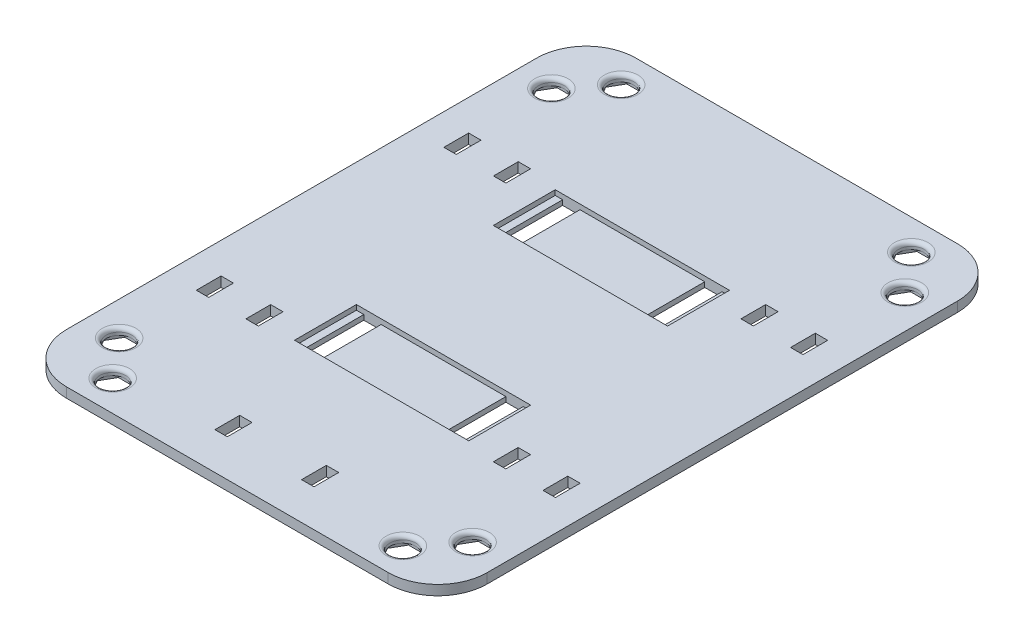
SolidWorks part; units mm, degrees
material "3-D Printed ABS"
ref_plane "Front Plane" through (0, 0, 0) normal (0, 0, 1) x (1, 0, 0)
ref_plane "Top Plane" through (0, 0, 0) normal (0, 1, 0) x (1, 0, 0)
ref_plane "Right Plane" through (0, 0, 0) normal (1, 0, 0) x (0, 0, -1)
sketch "Sketch1" plane through (0, 0, 0) normal (0, 1, 0) x (1, 0, 0)
  line L1 (-53.975, -73.025) -> (53.975, -73.025)
  line L2 (-53.975, -73.025) -> (-53.975, 73.025)
  line L3 (-53.975, 73.025) -> (53.975, 73.025)
  line L4 (53.975, -73.025) -> (53.975, 73.025)
  line L5 (-53.975, -73.025) -> (53.975, 73.025) construction
  line L6 (-53.975, 73.025) -> (53.975, -73.025) construction
  point P0 (0, 0)
  dimension "D1" = 107.95
  dimension "PlateY" = 146.05
extrude "Boss-Extrude1" add sketch "Sketch1" against normal blind 2.54
sketch "Sketch2" plane through (0, 0, 0) normal (0, 1, 0) x (1, 0, 0)
  line L0 (0, 0) -> (152.4, 0) construction
  line L1 (0, 0) -> (0, 152.4) construction
  line L4 (0, 0) -> (-53.975, 73.025) construction
  line L5 (0, 0) -> (-152.4, 0) construction
  line L6 (0, 0) -> (-152.4, 152.4) construction
  line L7 (-53.975, 73.025) -> (-53.975, -73.025) construction
  line L8 (53.975, 73.025) -> (-53.975, 73.025) construction
  line L9 (-152.4, 152.4) -> (-41.275, 60.325) construction
  line L10 (-41.275, 60.325) -> (0, 26.1257) construction
  line L11 (-30.7521, 73.025) -> (-53.975, 44.9974) construction
  circle A0 centre (-37.2189, 65.2108) radius 3.302
  circle A1 centre (45.3264, 55.4354) radius 3.302
  circle A2 centre (37.2189, 65.2108) radius 3.302
  circle A3 centre (-45.3264, -55.4354) radius 3.302
  circle A4 centre (-45.3264, 55.4354) radius 3.302
  circle A5 centre (-37.2189, -65.2108) radius 3.302
  circle A6 centre (37.2189, -65.2108) radius 3.302
  circle A7 centre (45.3264, -55.4354) radius 3.302
  point P12 (-41.275, 60.325)
  point P15 (-37.2189, 65.2108)
  dimension "D1" = 6.604
  dimension "D3" = 12.7
  dimension "D8" = 6.604
  dimension "D2" = 12.7
  dimension "D4" = 152.4
  dimension "D5" = 152.4
  dimension "D6" = 152.4
  dimension "D7" = 6.35
  dimension "D9" = 6.35
extrude "Cut-Extrude1" cut sketch "Sketch2" against normal through all
sketch "Sketch3" plane through (0, 0, 0) normal (0, 1, 0) x (1, 0, 0)
  line L0 (-53.975, 0) -> (53.975, 0) construction
  line L1 (-20.445, 33.4374) -> (-16, 33.4374)
  line L2 (-20.445, 33.4374) -> (-20.445, 17.5624)
  line L3 (-20.445, 17.5624) -> (-16, 17.5624)
  line L4 (-16, 33.4374) -> (-16, 17.5624)
  line L5 (16, 33.4374) -> (16, 17.5624)
  line L6 (20.445, 17.5624) -> (16, 17.5624)
  line L7 (20.445, 33.4374) -> (20.445, 17.5624)
  line L8 (20.445, 33.4374) -> (16, 33.4374)
  line L9 (-53.975, 73.025) -> (-53.975, -73.025) construction
  line L10 (53.975, -73.025) -> (53.975, 73.025) construction
  line L11 (0, -25.4999) -> (0, 79.6704) construction
  line L12 (0, 25.4999) -> (0, -79.6704) construction
  line L13 (20.445, -33.4374) -> (16, -33.4374)
  line L14 (20.445, -33.4374) -> (20.445, -17.5624)
  line L15 (20.445, -17.5624) -> (16, -17.5624)
  line L16 (16, -33.4374) -> (16, -17.5624)
  line L17 (-16, -33.4374) -> (-16, -17.5624)
  line L18 (-20.445, -17.5624) -> (-16, -17.5624)
  line L19 (-20.445, -33.4374) -> (-20.445, -17.5624)
  line L20 (-20.445, -33.4374) -> (-16, -33.4374)
  line L21 (-20.445, 25.4999) -> (-32.442, 25.4999) construction
  line L22 (-53.975, -73.025) -> (53.975, -73.025) construction
  point P31 (0, -73.025)
  point P32 (-53.975, 0)
  dimension "D1" = 15.875
  dimension "D2" = 4.445
  dimension "D3" = 16
  dimension "D4" = 25.4999
  dimension "D5" = 25.4999
extrude "Cut-Extrude2" cut sketch "Sketch3" against normal through all
fillet "Fillet1" radius 12.7 4 edges at (53.975, -1.27, -73.025) (53.975, -1.27, 73.025) (-53.975, -1.27, 73.025) (-53.975, -1.27, -73.025)
sketch "Sketch4" plane through (0, 0, 0) normal (0, 1, 0) x (1, 0, 0)
  line L0 (0, 0) -> (80.9727, -80.9727) construction
  line L1 (0, 0) -> (-80.9727, -80.9727) construction
  line L2 (69.1118, -51.1513) -> (28.7006, -10.7401)
  line L3 (28.7006, -10.7401) -> (10.7401, -28.7006)
  line L4 (10.7401, -28.7006) -> (51.1513, -69.1118)
  line L5 (51.1513, -69.1118) -> (69.1118, -51.1513)
  line L6 (0, 0) -> (0, -118.7381) construction
  line L7 (0, 0) -> (-98.4177, 0) construction
  line L8 (-51.1513, -69.1118) -> (-69.1118, -51.1513)
  line L9 (-69.1118, -51.1513) -> (-28.7006, -10.7401)
  line L10 (-28.7006, -10.7401) -> (-10.7401, -28.7006)
  line L11 (-10.7401, -28.7006) -> (-51.1513, -69.1118)
  line L12 (-69.1118, 51.1513) -> (-28.7006, 10.7401)
  line L13 (-51.1513, 69.1118) -> (-69.1118, 51.1513)
  line L14 (-10.7401, 28.7006) -> (-51.1513, 69.1118)
  line L15 (-28.7006, 10.7401) -> (-10.7401, 28.7006)
  line L16 (51.1513, 69.1118) -> (69.1118, 51.1513)
  line L17 (69.1118, 51.1513) -> (28.7006, 10.7401)
  line L18 (28.7006, 10.7401) -> (10.7401, 28.7006)
  line L19 (10.7401, 28.7006) -> (51.1513, 69.1118)
  point P6 (19.7204, -19.7204)
  dimension "D1" = 25.4
  dimension "D2" = 57.15
  dimension "D3" = 45
extrude "Cut-Extrude3" [suppressed] cut sketch "Sketch4" against normal blind 1.5875
sketch "Sketch6" [suppressed] plane through (0, 0, 0) normal (0, 1, 0) x (1, 0, 0)
  line L0 (46.3377, -44.1074) -> (34.6634, -32.4331) construction
  line L1 (0, 0) -> (0, -117.7376) construction
  line L2 (0, 0) -> (-151.7285, 0) construction
  line L4 (28.1601, -10.1996) -> (10.1996, -28.1601) construction
  line L5 (50.6107, -68.5712) -> (68.5712, -50.6107) construction
  text T0 "ESC" font "Century Gothic" height in points 22
  dimension "D1" = 45
  dimension "D2" = 20.32
  dimension "D3" = 20.32
extrude "Cut-Extrude5" [suppressed] cut sketch "Sketch6" against normal blind 3.175
sketch "Sketch5" plane through (0, 0, 0) normal (0, 1, 0) x (1, 0, 0)
  line L0 (41.275, 73.025) -> (-41.275, 73.025) construction
  line L1 (14.2875, 15.875) -> (-14.2875, 15.875)
  line L2 (14.2875, 15.875) -> (14.2875, 66.675)
  line L3 (14.2875, 66.675) -> (-14.2875, 66.675)
  line L4 (-14.2875, 15.875) -> (-14.2875, 66.675)
  point P4 (0, 15.875)
  dimension "D1" = 50.8
  dimension "D2" = 28.575
  dimension "D3" = 6.35
extrude "Cut-Extrude4" [suppressed] cut sketch "Sketch5" against normal blind 1.5875
ref_axis "Axis1" through (0, 0.3175, 0) along (0, -1, 0)
pattern_circular "CirPattern1" [suppressed] count 4 over 360 about axis through (0, 0.3175, 0) along (0, -1, 0) of bodies 105
sketch "Sketch7" plane through (0, 0, 0) normal (0, 1, 0) x (1, 0, 0)
  line L0 (0, 0) -> (0, -54.962) construction
  line L1 (63.4018, -13.3522) -> (38.0018, -13.3522)
  line L2 (63.4018, -13.3522) -> (63.4018, 43.7978)
  line L3 (63.4018, 43.7978) -> (38.0018, 43.7978)
  line L4 (38.0018, -13.3522) -> (38.0018, 43.7978)
  line L5 (-38.0018, -13.3522) -> (-38.0018, 43.7978)
  line L6 (-63.4018, 43.7978) -> (-38.0018, 43.7978)
  line L7 (-63.4018, -13.3522) -> (-63.4018, 43.7978)
  line L8 (-63.4018, -13.3522) -> (-38.0018, -13.3522)
  line L9 (-41.275, -73.025) -> (41.275, -73.025) construction
  line L10 (38.5677, -40.64) -> (-18.5823, -40.64)
  line L11 (38.5677, -40.64) -> (38.5677, -66.04)
  line L12 (38.5677, -66.04) -> (-18.5823, -66.04)
  line L13 (-18.5823, -40.64) -> (-18.5823, -66.04)
  line L14 (38.5677, -40.64) -> (-18.5823, -66.04) construction
  line L15 (38.5677, -66.04) -> (-18.5823, -40.64) construction
  line L16 (19.844, -36.1003) -> (-37.306, -36.1003)
  line L17 (19.844, -36.1003) -> (19.844, -61.5003)
  line L18 (19.844, -61.5003) -> (-37.306, -61.5003)
  line L19 (-37.306, -36.1003) -> (-37.306, -61.5003)
  line L20 (19.844, -36.1003) -> (-37.306, -61.5003) construction
  line L21 (19.844, -61.5003) -> (-37.306, -36.1003) construction
  point P11 (9.9927, -53.34)
  point P18 (-8.731, -48.8003)
  dimension "D1" = 57.15
  dimension "D2" = 25.4
  dimension "D3" = 57.15
  dimension "D4" = 25.4
  dimension "D5" = 6.985
  dimension "D6" = 57.15
  dimension "D7" = 25.4
extrude "Cut-Extrude6" [suppressed] cut sketch "Sketch7" against normal blind 1.27
sketch "Sketch8" plane through (0, 0, 0) normal (0, 1, 0) x (1, 0, 0)
  line L7 (19.05, -31.75) -> (-19.05, -31.75)
  line L8 (19.05, -31.75) -> (19.05, 31.75)
  line L9 (19.05, 31.75) -> (-19.05, 31.75)
  line L10 (-19.05, -31.75) -> (-19.05, 31.75)
  point P0 (0, 0)
  dimension "D1" = 38.1
  dimension "D2" = 31.75
  dimension "D3" = 63.5
extrude "Boss-Extrude3" [suppressed] add sketch "Sketch8" along normal blind 2.54
sketch "Sketch11" plane through (0, 0, 0) normal (0, 1, 0) x (1, 0, 0)
  line L0 (-20.445, -33.4374) -> (-16, -33.4374) construction
  line L1 (22.35, -33.4374) -> (-22.35, -33.4374)
  line L2 (22.35, -33.4374) -> (22.35, -17.5624)
  line L3 (22.35, -17.5624) -> (-22.35, -17.5624)
  line L4 (-22.35, -33.4374) -> (-22.35, -17.5624)
  line L5 (20.445, -17.5624) -> (16, -17.5624) construction
  line L6 (20.445, -33.4374) -> (20.445, -17.5624) construction
  line L7 (-20.445, -17.5624) -> (-20.445, -33.4374) construction
  line L8 (0, 0) -> (90.9737, 0) construction
  line L9 (-22.35, 33.4374) -> (-22.35, 17.5624)
  line L10 (22.35, 17.5624) -> (-22.35, 17.5624)
  line L11 (22.35, 33.4374) -> (22.35, 17.5624)
  line L12 (22.35, 33.4374) -> (-22.35, 33.4374)
  dimension "D1" = 1.905
  dimension "D2" = 1.905
extrude "Cut-Extrude9" cut sketch "Sketch11" against normal mid plane 2.54
sketch "Sketch12" plane through (0, 0, 0) normal (0, 1, 0) x (1, 0, 0)
  line L1 (12.7, -41.6354) -> (-12.7, -41.6354)
  line L2 (12.7, -41.6354) -> (12.7, -25.4999)
  line L3 (12.7, -25.4999) -> (-12.7, -25.4999)
  line L4 (-12.7, -41.6354) -> (-12.7, -25.4999)
  line L6 (23.8125, 0) -> (-23.8125, 0) construction
  line L7 (-53.975, 60.325) -> (-53.975, -60.325) construction
  line L9 (-12.7, 41.6354) -> (-12.7, 25.4999)
  line L10 (12.7, 25.4999) -> (-12.7, 25.4999)
  line L11 (12.7, 41.6354) -> (12.7, 25.4999)
  line L12 (12.7, 41.6354) -> (-12.7, 41.6354)
  point P6 (-53.975, 0)
  dimension "D1" = 25.4
  dimension "D2" = 25.4999
extrude "Cut-Extrude12" [suppressed] cut sketch "Sketch12" along normal through all
sketch "Sketch9" plane through (0, 0, 0) normal (0, 1, 0) x (1, 0, 0)
  line L1 (25.1579, -52.4084) -> (-25.6421, -52.4084)
  line L2 (25.1579, -52.4084) -> (25.1579, -1.6084)
  line L3 (25.1579, -1.6084) -> (-25.6421, -1.6084)
  line L4 (-25.6421, -52.4084) -> (-25.6421, -1.6084)
  line L5 (25.1579, -52.4084) -> (-25.6421, -1.6084) construction
  line L6 (25.1579, -1.6084) -> (-25.6421, -52.4084) construction
  point P0 (-0.2421, -27.0084)
  dimension "D1" = 50.8
  dimension "D2" = 50.8
sketch "Sketch13" plane through (0, 0, 0) normal (0, 1, 0) x (1, 0, 0)
  line L0 (0, 0) -> (0, -106.7514) construction
  line L1 (34.925, 3.175) -> (28.575, 3.175)
  line L2 (34.925, 3.175) -> (34.925, -3.175)
  line L3 (34.925, -3.175) -> (28.575, -3.175)
  line L4 (28.575, 3.175) -> (28.575, -3.175)
  line L5 (34.925, 3.175) -> (28.575, -3.175) construction
  line L6 (34.925, -3.175) -> (28.575, 3.175) construction
  line L7 (-34.925, -3.175) -> (-28.575, 3.175) construction
  line L8 (-34.925, 3.175) -> (-28.575, -3.175) construction
  line L9 (-28.575, 3.175) -> (-28.575, -3.175)
  line L10 (-34.925, -3.175) -> (-28.575, -3.175)
  line L11 (-34.925, 3.175) -> (-34.925, -3.175)
  line L12 (-34.925, 3.175) -> (-28.575, 3.175)
  point P0 (31.75, 0)
  point P12 (-31.75, 0)
  dimension "D1" = 6.35
  dimension "D2" = 28.575
  dimension "D3" = 0
extrude "Cut-Extrude13" [suppressed] cut sketch "Sketch13" against normal through all
fillet "Fillet2" radius 1.016 8 edges at (-37.2189, 0, -61.9088) (37.2189, 0, 68.5128) (45.3264, 0, 58.7374) (-37.2189, 0, 61.9088) (-45.3264, 0, 52.1334) (45.3264, 0, -58.7374) (37.2189, 0, -68.5128) (-45.3264, 0, -52.1334)
sketch "Sketch14" plane through (0, 0, 0) normal (0, 1, 0) x (1, 0, 0)
  line L0 (0, 76.698) -> (0, -76.698) construction
  line L1 (33.3248, -34.925) -> (30.1498, -34.925)
  line L2 (33.3248, -34.925) -> (33.3248, -28.575)
  line L3 (33.3248, -28.575) -> (30.1498, -28.575)
  line L4 (30.1498, -34.925) -> (30.1498, -28.575)
  line L5 (0, 0) -> (-92.4571, 0) construction
  line L6 (-30.1498, -34.925) -> (-30.1498, -28.575)
  line L7 (-33.3248, -28.575) -> (-30.1498, -28.575)
  line L8 (-33.3248, -34.925) -> (-33.3248, -28.575)
  line L9 (-33.3248, -34.925) -> (-30.1498, -34.925)
  line L10 (-33.3248, 34.925) -> (-30.1498, 34.925)
  line L11 (-33.3248, 34.925) -> (-33.3248, 28.575)
  line L12 (-33.3248, 28.575) -> (-30.1498, 28.575)
  line L13 (-30.1498, 34.925) -> (-30.1498, 28.575)
  line L14 (30.1498, 34.925) -> (30.1498, 28.575)
  line L15 (33.3248, 28.575) -> (30.1498, 28.575)
  line L16 (33.3248, 34.925) -> (33.3248, 28.575)
  line L17 (33.3248, 34.925) -> (30.1498, 34.925)
  line L18 (-41.275, -73.025) -> (41.275, -73.025) construction
  line L19 (-9.525, -63.5) -> (-9.525, -57.15)
  line L20 (12.7, -63.5) -> (9.525, -63.5)
  line L21 (12.7, -63.5) -> (12.7, -57.15)
  line L22 (12.7, -57.15) -> (9.525, -57.15)
  line L23 (38.1, -73.025) -> (38.1, 73.025) construction
  line L24 (41.275, 73.025) -> (-41.275, 73.025) construction
  line L25 (42.8752, 34.925) -> (46.0502, 34.925)
  line L26 (42.8752, 34.925) -> (42.8752, 28.575)
  line L27 (42.8752, 28.575) -> (46.0502, 28.575)
  line L28 (46.0502, 34.925) -> (46.0502, 28.575)
  line L29 (46.0502, -34.925) -> (46.0502, -28.575)
  line L30 (42.8752, -28.575) -> (46.0502, -28.575)
  line L31 (42.8752, -34.925) -> (42.8752, -28.575)
  line L32 (42.8752, -34.925) -> (46.0502, -34.925)
  line L33 (-46.0502, 34.925) -> (-46.0502, 28.575)
  line L34 (-42.8752, 28.575) -> (-46.0502, 28.575)
  line L35 (-42.8752, 34.925) -> (-42.8752, 28.575)
  line L36 (-42.8752, 34.925) -> (-46.0502, 34.925)
  line L37 (-42.8752, -34.925) -> (-46.0502, -34.925)
  line L38 (-42.8752, -34.925) -> (-42.8752, -28.575)
  line L39 (-42.8752, -28.575) -> (-46.0502, -28.575)
  line L40 (-46.0502, -34.925) -> (-46.0502, -28.575)
  line L41 (53.975, -50.8) -> (-53.975, -50.8) construction
  line L42 (53.975, -60.325) -> (53.975, 60.325) construction
  line L43 (-53.975, 60.325) -> (-53.975, -60.325) construction
  line L44 (0, -178.298) -> (0, -24.902) construction
  line L45 (9.525, -63.5) -> (9.525, -57.15)
  line L46 (-12.7, -57.15) -> (-9.525, -57.15)
  line L47 (-12.7, -63.5) -> (-12.7, -57.15)
  line L48 (-12.7, -63.5) -> (-9.525, -63.5)
  dimension "D2" = 3.175
  dimension "D3" = 6.35
  dimension "D4" = 28.575
  dimension "D5" = 3.175
  dimension "D6" = 6.35
  dimension "D7" = 9.525
  dimension "D8" = 9.525
  dimension "D9" = 38.1
  dimension "D10" = 22.225
  dimension "D11" = 30.1498
extrude "Cut-Extrude14" cut sketch "Sketch14" against normal through all
sketch "Sketch17" plane through (0, -2.54, 0) normal (0, -1, 0) x (1, 0, 0)
  line L0 (0, 0) -> (-152.4, 0) construction
  line L1 (0, 0) -> (0, -152.4) construction
  line L2 (0, -152.4) -> (-152.4, -152.4) construction
  line L3 (-152.4, -152.4) -> (-152.4, 0) construction
  line L4 (-152.4, -152.4) -> (0, 0) construction
  line L5 (41.275, -73.025) -> (-41.275, -73.025) construction
  line L6 (-53.975, -60.325) -> (-53.975, 60.325) construction
  line L7 (-152.4, -152.4) -> (-41.275, -60.325) construction
  line L8 (-41.275, -60.325) -> (0, -26.1257) construction
  line L9 (43.3467, -52.0064) -> (47.3061, -52.0064)
  line L10 (-41.3669, -55.4354) -> (-43.3467, -52.0064)
  line L11 (-43.3467, -52.0064) -> (-47.3061, -52.0064)
  line L12 (-47.3061, -52.0064) -> (-49.2859, -55.4354)
  line L13 (-49.2859, -55.4354) -> (-47.3061, -58.8644)
  line L14 (-47.3061, -58.8644) -> (-43.3467, -58.8644)
  line L15 (-43.3467, -58.8644) -> (-41.3669, -55.4354)
  line L16 (-33.2595, -65.2108) -> (-35.2392, -61.7818)
  line L17 (-35.2392, -61.7818) -> (-39.1987, -61.7818)
  line L18 (-39.1987, -61.7818) -> (-41.1784, -65.2108)
  line L19 (-41.1784, -65.2108) -> (-39.1987, -68.6398)
  line L20 (-39.1987, -68.6398) -> (-35.2392, -68.6398)
  line L21 (-35.2392, -68.6398) -> (-33.2595, -65.2108)
  line L22 (47.3061, -52.0064) -> (49.2859, -55.4354)
  line L23 (49.2859, -55.4354) -> (47.3061, -58.8644)
  line L24 (41.3669, -55.4354) -> (43.3467, -52.0064)
  line L25 (43.3467, -58.8644) -> (41.3669, -55.4354)
  line L26 (47.3061, -58.8644) -> (43.3467, -58.8644)
  line L27 (35.2392, -61.7818) -> (39.1987, -61.7818)
  line L28 (33.2595, -65.2108) -> (35.2392, -61.7818)
  line L29 (39.1987, -61.7818) -> (41.1784, -65.2108)
  line L30 (41.1784, -65.2108) -> (39.1987, -68.6398)
  line L31 (35.2392, -68.6398) -> (33.2595, -65.2108)
  line L32 (39.1987, -68.6398) -> (35.2392, -68.6398)
  line L33 (-41.3669, 55.4354) -> (-43.3467, 52.0064)
  line L34 (-43.3467, 52.0064) -> (-47.3061, 52.0064)
  line L35 (-47.3061, 52.0064) -> (-49.2859, 55.4354)
  line L36 (-49.2859, 55.4354) -> (-47.3061, 58.8644)
  line L37 (-47.3061, 58.8644) -> (-43.3467, 58.8644)
  line L38 (-43.3467, 58.8644) -> (-41.3669, 55.4354)
  line L39 (-33.2595, 65.2108) -> (-35.2392, 61.7818)
  line L40 (-35.2392, 61.7818) -> (-39.1987, 61.7818)
  line L41 (-39.1987, 61.7818) -> (-41.1784, 65.2108)
  line L42 (-41.1784, 65.2108) -> (-39.1987, 68.6398)
  line L43 (-39.1987, 68.6398) -> (-35.2392, 68.6398)
  line L44 (-35.2392, 68.6398) -> (-33.2595, 65.2108)
  line L45 (39.1987, 68.6398) -> (35.2392, 68.6398)
  line L46 (35.2392, 68.6398) -> (33.2595, 65.2108)
  line L47 (41.1784, 65.2108) -> (39.1987, 68.6398)
  line L48 (39.1987, 61.7818) -> (41.1784, 65.2108)
  line L49 (33.2595, 65.2108) -> (35.2392, 61.7818)
  line L50 (35.2392, 61.7818) -> (39.1987, 61.7818)
  line L51 (47.3061, 58.8644) -> (43.3467, 58.8644)
  line L52 (43.3467, 58.8644) -> (41.3669, 55.4354)
  line L53 (41.3669, 55.4354) -> (43.3467, 52.0064)
  line L54 (49.2859, 55.4354) -> (47.3061, 58.8644)
  line L55 (47.3061, 52.0064) -> (49.2859, 55.4354)
  line L56 (43.3467, 52.0064) -> (47.3061, 52.0064)
  circle A0 centre (-45.3264, -55.4354) radius 3.429 construction
  circle A1 centre (-37.2189, -65.2108) radius 3.429 construction
  point P0 (0, 0)
  point P6 (-41.275, -60.2488)
  dimension "D1" = 12.7762
  dimension "D2" = 12.7
  dimension "D3" = 6.858
  dimension "D4" = 6.858
extrude "Cut-Extrude15" cut sketch "Sketch17" against normal blind 0.7937
equation "\"Plate Dim Y\"= \"Plate Dim Y@Quad Assemb.SLDASM\""
equation "\"PlateY@Sketch1\" = \"Plate Dim Y\""
equation "\"D1@Sketch1\"= \"Plate Dim X\""
equation "\"D1@Boss-Extrude1\" = \"Plate Thickness\""
equation "\"Plate Dim X\"= \"Plate Dim X@Quad Assemb.SLDASM\""
equation "\"Plate Thickness\"= \"Plate Thickness@Quad Assemb.sldasm\""
equation "\"Batt X\"= \"Batt X@Quad Assemb.sldasm\""
equation "\"Batt Y\"= \"Batt Y@Quad Assemb.sldasm\""
equation "\"D3@Sketch3\"=\"Batt X\"/2"
equation "\"D4@Sketch3\"=\"Batt Y\"/4"
equation "\"D5@Sketch3\"=\"Batt Y\"*2/8"
equation "\"Dowell Width\"= \"Dowell Width@Quad Assemb.sldasm\""
equation "\"D1@Sketch2\"=\"Dowell Width\"+.01"
equation "\"D2@Sketch12\"=\"Batt Y\"/4"
equation "\"D7@Sketch2\"=\"Dowell Width\""
equation "\"D8@Sketch2\"=\"Dowell Width\" +0.01in"
equation "\"D9@Sketch2\"=\"Dowell Width\""
